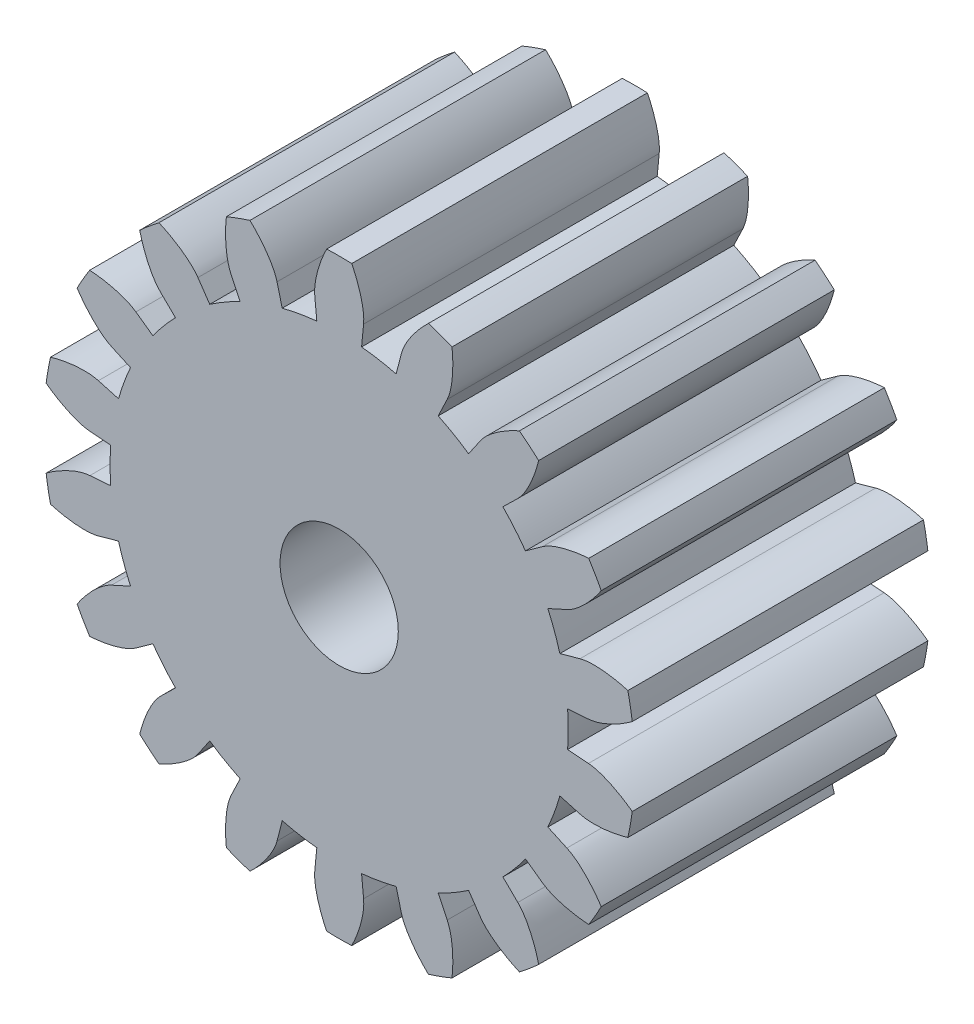
SolidWorks part; units mm, degrees
ref_plane "前视基准面" through (0, 0, 0) normal (0, 0, 1) x (1, 0, 0)
ref_plane "上视基准面" through (0, 0, 0) normal (0, 1, 0) x (1, 0, 0)
ref_plane "右视基准面" through (0, 0, 0) normal (1, 0, 0) x (0, 0, -1)
other "Configuration Table"
sketch "草图1" plane through (0, 0, 0) normal (0, 0, 1) x (1, 0, 0)
  line L0 (0, 0) -> (4.5, 0) construction
  line L1 (0, 0) -> (4.4829, 0.3922) construction
  line L2 (0, 0) -> (4.2162, 0.3242)
  line L3 (4.4829, 0.3922) -> (4.4829, -0.3922) construction
  line L4 (0, 0) -> (4.2162, -0.3242)
  circle A0 centre (0, 0) radius 5
  circle A1 centre (0, 0) radius 4.5 construction
  circle A2 centre (0, 0) radius 3.875
  circle A3 centre (0, 0) radius 4.2286 construction
  circle A4 centre (0, 0) radius 1
  spline S0 degree 4 poles (4.2162, 0.3242) (4.2483, 0.3267) (4.3375, 0.3403) (4.5024, 0.3926) (4.7554, 0.5133) (5.0556, 0.719) (5.3996, 1.035) (5.7429, 1.4621) (6.0488, 1.9801) (6.3604, 2.7282) (6.5454, 3.5193) (6.6174, 4.3594) (6.5658, 5.3616) (6.386, 6.3504) (6.0115, 7.457) (5.4105, 8.6071) (4.6509, 9.6584) (3.7565, 10.5972) (2.7501, 11.414) (1.6521, 12.1025) (0.4824, 12.659) (-0.5894, 13.0292) (-1.4522, 13.2437) (-2.0892, 13.3611) (-2.4865, 13.4209) (-2.8127, 13.4604) (-3.1237, 13.492) (-3.465, 13.5153) (-3.7294, 13.5295) (-4.0312, 13.5361) (-4.338, 13.5384) (-4.6432, 13.533) (-5.1827, 13.5111) (-5.559, 13.4725) (-5.9997, 13.426) (-6.2265, 13.3891) (-6.3687, 13.3688) (-6.431, 13.3583) knots 0 0 0 0 0 0.005604 0.015718 0.02996 0.048734 0.068727 0.096889 0.125051 0.153212 0.209535 0.237696 0.271429 0.327752 0.384075 0.440398 0.496721 0.553044 0.609367 0.66569 0.722013 0.778336 0.806497 0.820578 0.834659 0.84874 0.86282 0.876901 0.890982 0.900036 0.909091 0.931818 0.954545 0.977273 0.988636 1 1 1 1 1 construction
  spline S1 degree 4 poles (4.2162, 0.3242) (4.2483, 0.3267) (4.3375, 0.3403) (4.5024, 0.3926) (4.7554, 0.5133) (5.0556, 0.719) (5.3996, 1.035) (5.7429, 1.4621) (6.0488, 1.9801) (6.3604, 2.7282) (6.5454, 3.5193) (6.6174, 4.3594) (6.5658, 5.3616) (6.386, 6.3504) (6.0115, 7.457) (5.4105, 8.6071) (4.6509, 9.6584) (3.7565, 10.5972) (2.7501, 11.414) (1.6521, 12.1025) (0.4824, 12.659) (-0.5894, 13.0292) (-1.4522, 13.2437) (-2.0892, 13.3611) (-2.4865, 13.4209) (-2.8127, 13.4604) (-3.1237, 13.492) (-3.465, 13.5153) (-3.7294, 13.5295) (-4.0312, 13.5361) (-4.2111, 13.5375) (-4.3059, 13.5372) (-4.3531, 13.5368) knots 0 0 0 0 0 0.005604 0.015718 0.02996 0.048734 0.068727 0.096889 0.125051 0.153212 0.209535 0.237696 0.271429 0.327752 0.384075 0.440398 0.496721 0.553044 0.609367 0.66569 0.722013 0.778336 0.806497 0.820578 0.834659 0.84874 0.86282 0.876901 0.890982 0.900036 0.909091 0.909091 0.909091 0.909091 0.909091
  spline S2 degree 4 poles (4.2162, -0.3242) (4.2483, -0.3267) (4.3375, -0.3403) (4.5024, -0.3926) (4.7554, -0.5133) (5.0556, -0.719) (5.3996, -1.035) (5.7429, -1.4621) (6.0488, -1.9801) (6.3604, -2.7282) (6.5454, -3.5193) (6.6174, -4.3594) (6.5658, -5.3616) (6.386, -6.3504) (6.0115, -7.457) (5.4105, -8.6071) (4.6509, -9.6584) (3.7565, -10.5972) (2.7501, -11.414) (1.6521, -12.1025) (0.4824, -12.659) (-0.5894, -13.0292) (-1.4522, -13.2437) (-2.0892, -13.3611) (-2.4865, -13.4209) (-2.8127, -13.4604) (-3.1237, -13.492) (-3.465, -13.5153) (-3.7294, -13.5295) (-4.0312, -13.5361) (-4.338, -13.5384) (-4.6432, -13.533) (-5.1827, -13.5111) (-5.559, -13.4725) (-5.9997, -13.426) (-6.2265, -13.3891) (-6.3687, -13.3688) (-6.431, -13.3583) knots 0 0 0 0 0 0.005604 0.015718 0.02996 0.048734 0.068727 0.096889 0.125051 0.153212 0.209535 0.237696 0.271429 0.327752 0.384075 0.440398 0.496721 0.553044 0.609367 0.66569 0.722013 0.778336 0.806497 0.820578 0.834659 0.84874 0.86282 0.876901 0.890982 0.900036 0.909091 0.931818 0.954545 0.977273 0.988636 1 1 1 1 1 construction
  spline S3 degree 4 poles (4.2162, -0.3242) (4.2483, -0.3267) (4.3375, -0.3403) (4.5024, -0.3926) (4.7554, -0.5133) (5.0556, -0.719) (5.3996, -1.035) (5.7429, -1.4621) (6.0488, -1.9801) (6.3604, -2.7282) (6.5454, -3.5193) (6.6174, -4.3594) (6.5658, -5.3616) (6.386, -6.3504) (6.0115, -7.457) (5.4105, -8.6071) (4.6509, -9.6584) (3.7565, -10.5972) (2.7501, -11.414) (1.6521, -12.1025) (0.4824, -12.659) (-0.5894, -13.0292) (-1.4522, -13.2437) (-2.0892, -13.3611) (-2.4865, -13.4209) (-2.8127, -13.4604) (-3.1237, -13.492) (-3.465, -13.5153) (-3.7294, -13.5295) (-4.0312, -13.5361) (-4.2111, -13.5375) (-4.3059, -13.5372) (-4.3531, -13.5368) knots 0 0 0 0 0 0.005604 0.015718 0.02996 0.048734 0.068727 0.096889 0.125051 0.153212 0.209535 0.237696 0.271429 0.327752 0.384075 0.440398 0.496721 0.553044 0.609367 0.66569 0.722013 0.778336 0.806497 0.820578 0.834659 0.84874 0.86282 0.876901 0.890982 0.900036 0.909091 0.909091 0.909091 0.909091 0.909091
  point P15 (4.4829, 0)
  dimension "齿顶圆直径" = 10
  dimension "分度圆直径" = 9
  dimension "齿根圆直径" = 7.75
  dimension "基圆直径" = 8.4572
  dimension "内孔直径" = 2
  dimension "渐近线镜像线夹角" = 5
extrude "凸台-拉伸1" add sketch "草图1" along normal blind 5 contours A0 | A4
extrude "切除-拉伸1" cut sketch "草图1<3>" along normal through all contours A2 S3 A0 S1 region at (4.5106, 0, 0)
sketch "草图1<3>" plane through (0, 0, 0) normal (0, 0, 1) x (1, 0, 0) same geometry as "草图1"
pattern_circular "阵列(圆周)1" count 18 every 20 about axis through (0, 0, 5) along (0, 0, 1) of "切除-拉伸1"
equation "\"m\"= 0.5'模数"
equation "\"z\" = 18'齿数"
equation "\"a\"= 20度'压力角"
equation "\"d\"= \"m\" * \"z\"'分度圆直径"
equation "\"da\"= ( \"z\" + 2 ) * \"m\"'齿顶圆直径"
equation "\"df\"= ( \"z\" - 2.5 ) * \"m\"'齿根圆直径"
equation "\"s\"= 0.5 * PI * \"m\"'分度圆齿厚"
equation "\"r\"= 0.38 * \"m\"'齿根圆角"
equation "\"B\"= 0.3 * \"d\"'齿厚"
equation "\"db\"= \"m\" * \"z\" * cos ( \"a\" )'基圆直径"
equation "\"rb\"= \"db\" / 2'基圆半径"
equation "\"齿顶圆直径@草图1\"= \"da\""
equation "\"分度圆直径@草图1\"= \"d\""
equation "\"齿根圆直径@草图1\"= \"df\""
equation "\"基圆直径@草图1\"= \"db\""
equation "\"渐近线镜像线夹角@草图1\"= 360 / 4 / \"z\""
equation "\"h\"= 5'齿轮厚度"
equation "\"ir\"= 2'内孔直径"
equation "\"内孔直径@草图1\"= \"ir\""
equation "\"齿轮厚@凸台-拉伸1\"= \"h\""
equation "\"齿轮夹角@阵列(圆周)1\"= 360 / \"z\""
equation "\"齿数@阵列(圆周)1\"= \"z\""
